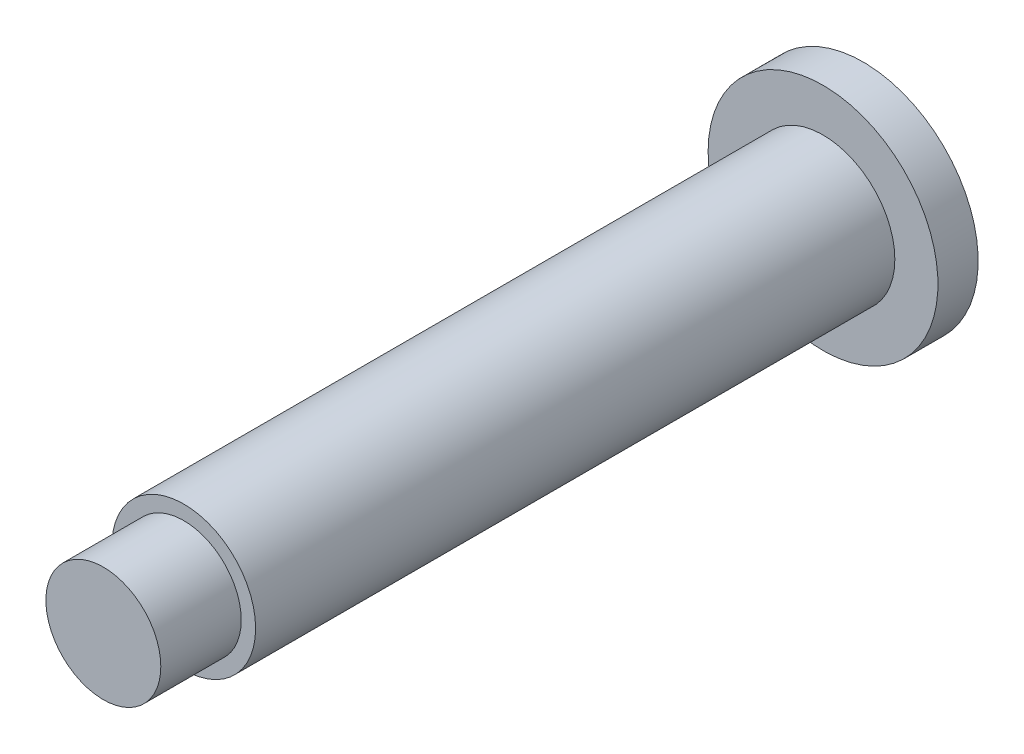
SolidWorks part; units mm, degrees
ref_plane "Front Plane" through (0, 0, 0) normal (1, 0, 0) x (0, 1, 0)
ref_plane "Top Plane" through (0, 0, 0) normal (0, 0, 1) x (0, 1, 0)
ref_plane "Right Plane" through (0, 0, 0) normal (0, 1, 0) x (-1, 0, 0)
sketch "Sketch1" plane through (0, 0, 0) normal (0, 0, 1) x (0, 1, 0)
  circle A0 centre (0, 0) radius 2.5
extrude "Boss-Extrude1" add sketch "Sketch1" along normal blind 22.25 contours A0
sketch "Sketch2" plane through (0, 0, 0) normal (0, 0, -1) x (1, 0, 0)
  circle A0 centre (0, 0) radius 4
extrude "Boss-Extrude2" add sketch "Sketch2" along normal blind 1.4
sketch "Sketch3" plane through (0, 0, -1.4) normal (0, 0, -1) x (1, 0, 0)
  circle A0 centre (0, 0) radius 2.05
extrude "Cut-Extrude1" cut sketch "Sketch3" against normal blind 3
sketch "Sketch4" plane through (0, 0, 22.25) normal (0, 0, 1) x (1, 0, 0)
  circle A0 centre (0, 0) radius 2
extrude "Boss-Extrude3" add sketch "Sketch4" along normal blind 2.8
equation "\"whitekey_cutout_length\"= 101.5"
equation "\"key_mount_recess_length\"=50"
equation "\"key_mount_recess_height\"=12.5"
equation "\"key_mount_recess_depth\"=1.5"
equation "\"wall_thickness\"=10"
equation "\"guide_brace_height\"=20"
equation "\"guide_brace_thickness\"=2"
equation "\"dowel_recess_depth\"=9"
equation "\"dowel_recess_offset\"=3"
equation "\"base_mount_height\"=40"
equation "\"base_rear_length\"=80"
equation "\"base_front_length\"=111.5"
equation "\"screw_hole_wall_offset\"=7.25"
equation "\"screw_hole_edge_inset\"=4.5"
equation "\"screw_hole_diameter\"=3.8"
equation "\"screw_head_hole_diameter\"=6.7"
equation "\"screw_nut_hole_side_len\"=3.5"
equation "\"screw_nut_recess_offset\"=0.3"
equation "\"screw_head_and_nut_recess_depth\"=2.5"
equation "\"screw_shaft_diameter\"=3.5"
equation "\"switch_board_width\"=30"
equation "\"switch_board_wall_offset\"=11.5"
equation "\"heatset_insert_hole_diameter\"=4.8"
equation "\"heatset_insert_hole_depth\"=3.8"
equation "\"front_rear_panel_width\"=23.75"
equation "\"rod_length_adj\"=0.5"
equation "\"rod_insert_length\"=2.8"
equation "\"D1@Boss-Extrude1\"=\"rod_length_adj\"+21.75mm"
equation "\"D1@Boss-Extrude2\"=2-\"rod_length_adj\"-0.1"
equation "\"D1@Boss-Extrude3\"=\"rod_insert_length\""
